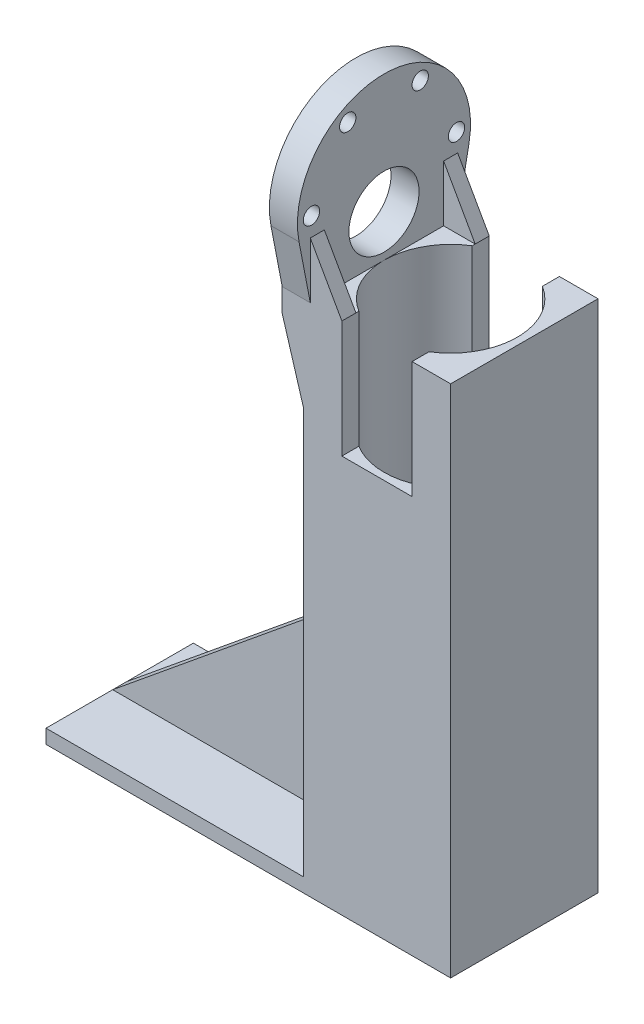
SolidWorks part; units mm, degrees
material "PET"
ref_plane "Front Plane" through (0, 0, 0) normal (0, 0, 1) x (1, 0, 0)
ref_plane "Top Plane" through (0, 0, 0) normal (0, 1, 0) x (1, 0, 0)
ref_plane "Right Plane" through (0, 0, 0) normal (1, 0, 0) x (0, 0, -1)
sketch "Sketch1" plane through (0, 0, 0) normal (0, 1, 0) x (1, 0, 0)
  line L1 (0, 0) -> (31.5, 0)
  line L2 (0, 0) -> (0, -31.5)
  line L3 (0, -31.5) -> (31.5, -31.5)
  line L4 (31.5, 0) -> (31.5, -31.5)
  point P5 (-83.1406, 4.6759)
  point P7 (28.1819, -15.5)
  dimension "D1" = 31.5
  dimension "D5" = 31.5
extrude "Boss-Extrude1" add sketch "Sketch1" along normal blind 110 contours L1 L4 L3 L2
sketch "Sketch2" plane through (0, 110, 0) normal (0, 1, 0) x (1, 0, 0)
  line L0 (0, 0) -> (31.5, 0) construction
  line L1 (31.5, 0) -> (31.5, -31.5) construction
  circle A0 centre (15.75, -15.75) radius 14.25
  dimension "D1" = 28.5
  dimension "D2" = 15.75
  dimension "D3" = 15.75
extrude "Cut-Extrude1" cut sketch "Sketch2" against normal blind 108
sketch "Sketch4" plane through (0, 0, 0) normal (-1, 0, 0) x (0, 0, 1)
  line L0 (0, 110) -> (31.5, 110) construction
  line L1 (0, 110) -> (0, 0) construction
  line L2 (33.9139, 122.4894) -> (31.5, 110)
  line L3 (31.5, 110) -> (25.0371, 110)
  line L4 (-2.4139, 122.4894) -> (0, 110)
  line L5 (0, 110) -> (6.4629, 110)
  arc A0 (33.9139, 122.4894) -> (-2.4139, 122.4894) centre (15.75, 126) ccw
  arc A1 (6.4629, 110) -> (25.0371, 110) centre (15.75, 126) ccw
  dimension "D1" = 37
  dimension "D2" = 16
  dimension "D3" = 15.75
extrude "Boss-Extrude2" add sketch "Sketch4" against normal blind 1.5 contours A0 L4 L5 A1 L3 L2
extrude "Boss-Extrude3" add sketch "Sketch4<3>" against normal blind 1.5
sketch "Sketch4<3>" plane through (0, 0, 0) normal (-1, 0, 0) x (0, 0, 1) same geometry as "Sketch4"
sketch "Sketch6" plane through (0, 0, 31.5) normal (0, 0, 1) x (1, 0, 0)
  line L3 (0, 110) -> (0, 0) construction
  line L4 (0, 90) -> (0, 110)
  line L6 (0, 110) -> (-4.5, 110)
  line L7 (-4.5, 110) -> (-4.5, 105)
  line L8 (-4.5, 105) -> (0, 90)
  dimension "D1" = 4.5
  dimension "D2" = 20
  dimension "D3" = 5
extrude "Boss-Extrude4" add sketch "Sketch6" against normal up to surface (31.5 mm away) up to face at (12.9, 66, 0)
sketch "Sketch10" plane through (0, 0, 0) normal (-1, 0, 0) x (0, 0, 1)
  line L0 (0, 90) -> (0, 0) construction
  line L1 (31.5, 0) -> (0, 0)
  line L2 (31.5, 0) -> (31.5, 3)
  line L3 (31.5, 3) -> (0, 3)
  line L4 (0, 0) -> (0, 3)
  dimension "D1" = 3
extrude "Boss-Extrude5" add sketch "Sketch10" along normal blind 55
ref_plane "Plane1" through (0, 0, 15.75) normal (0, 0, -1) x (-1, 0, 0)
sketch "Sketch9" plane through (0, 110, 0) normal (0, 1, 0) x (1, 0, 0)
  line L0 (1.5, -31.5) -> (31.5, -31.5) construction
  line L1 (23.25, -31.5) -> (8.25, -31.5)
  line L2 (23.25, -31.5) -> (23.25, 0)
  line L3 (23.25, 0) -> (8.25, 0)
  line L4 (8.25, -31.5) -> (8.25, 0)
  line L5 (1.5, 0) -> (31.5, 0) construction
  line L6 (31.5, 0) -> (31.5, -31.5) construction
  dimension "D1" = 15
  dimension "D2" = 23.25
extrude "Cut-Extrude4" cut sketch "Sketch9" against normal blind 25
sketch "Sketch14" plane through (0, 0, 15.75) normal (0, 0, -1) x (-1, 0, 0)
  line L0 (55, 3) -> (0, 48)
  line L1 (0, 90) -> (0, 3) construction
  line L2 (0, 48) -> (0, 3)
  line L3 (0, 3) -> (55, 3)
extrude "Boss-Extrude6" add sketch "Sketch14" along normal mid plane 3
sketch "Sketch15" plane through (0, 0, 31.5) normal (0, 0, 1) x (1, 0, 0)
  line L0 (8.25, 110) -> (1.5, 110)
  line L1 (1.5, 110) -> (1.5, 122)
  line L2 (1.5, 122) -> (8.25, 110)
  dimension "D1" = 12
extrude "Boss-Extrude7" add sketch "Sketch15" against normal blind 3
sketch "Sketch16" plane through (0, 0, 0) normal (0, 0, -1) x (-1, 0, 0)
  line L0 (-8.25, 110) -> (-1.5, 110)
  line L1 (-1.5, 110) -> (-1.5, 122)
  line L2 (-1.5, 122) -> (-8.25, 110)
  dimension "D1" = 12
extrude "Boss-Extrude8" add sketch "Sketch16" against normal blind 3
extrude "Boss-Extrude9" add sketch "Sketch4<4>" along normal blind 4.5
sketch "Sketch4<4>" plane through (0, 0, 0) normal (-1, 0, 0) x (0, 0, 1) same geometry as "Sketch4"
sketch "Sketch7" plane through (1.5, 0, 0) normal (1, 0, 0) x (0, 0, -1)
  circle A0 centre (-15.75, 126) radius 15.5 construction
  circle A1 centre (-31.25, 126) radius 1.75
  circle A2 centre (-23.5, 139.4234) radius 1.75
  circle A3 centre (-8, 139.4234) radius 1.75
  circle A4 centre (-0.25, 126) radius 1.75
  circle A5 centre (-15.75, 119) radius 7.5
  point P13 (-15.75, 126)
  dimension "D1" = 4
  dimension "D2" = 7
  dimension "D3" = 15
extrude "Cut-Extrude3" cut sketch "Sketch7" against normal mid plane 34.5
